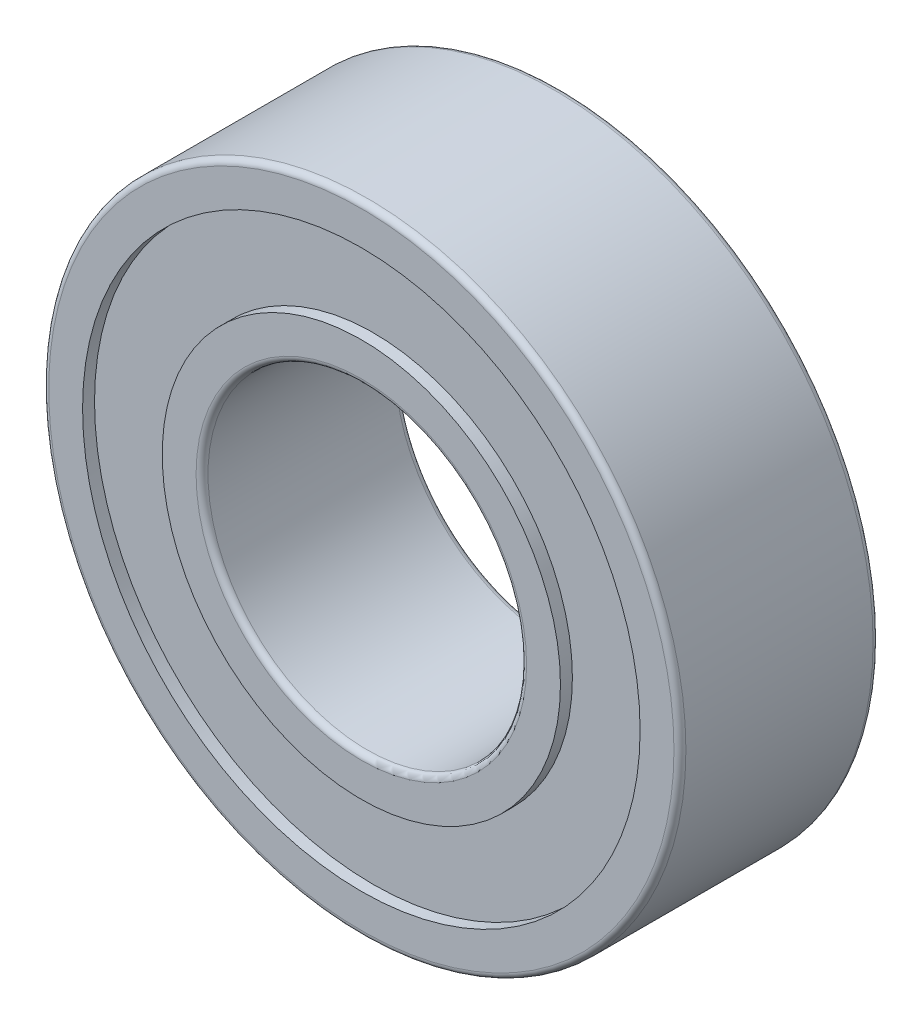
SolidWorks part; units mm, degrees
ref_plane "Front Plane" through (0, 0, 0) normal (0, 0, 1) x (1, 0, 0)
ref_plane "Top Plane" through (0, 0, 0) normal (0, 1, 0) x (1, 0, 0)
ref_plane "Right Plane" through (0, 0, 0) normal (1, 0, 0) x (0, 0, -1)
sketch "Sketch1" plane through (0, 0, 0) normal (0, 0, 1) x (1, 0, 0)
  circle A0 centre (0, 0) radius 4
  circle A1 centre (0, 0) radius 8
  dimension "D1" = 8
  dimension "D2" = 16
extrude "Boss-Extrude1" add sketch "Sketch1" along normal blind 5
sketch "Sketch2" plane through (0, 0, 5) normal (0, 0, 1) x (1, 0, 0)
  circle A3 centre (0, 0) radius 7
  circle A6 centre (0, 0) radius 5
  dimension "D1" = 10
  dimension "D2" = 14
extrude "Cut-Extrude1" cut sketch "Sketch2" against normal blind 0.3
extrude "Cut-Extrude2" cut sketch "Sketch2<2>" along normal blind 0.5 from surface starting at face at (8, 0, 0)
sketch "Sketch2<2>" plane through (0, 0, 5) normal (0, 0, 1) x (1, 0, 0) same geometry as "Sketch2"
fillet "Fillet1" radius 0.15 4 edges at (4, 0, 5) (8, 0, 5) (4, 0, 0) (8, 0, 0)
